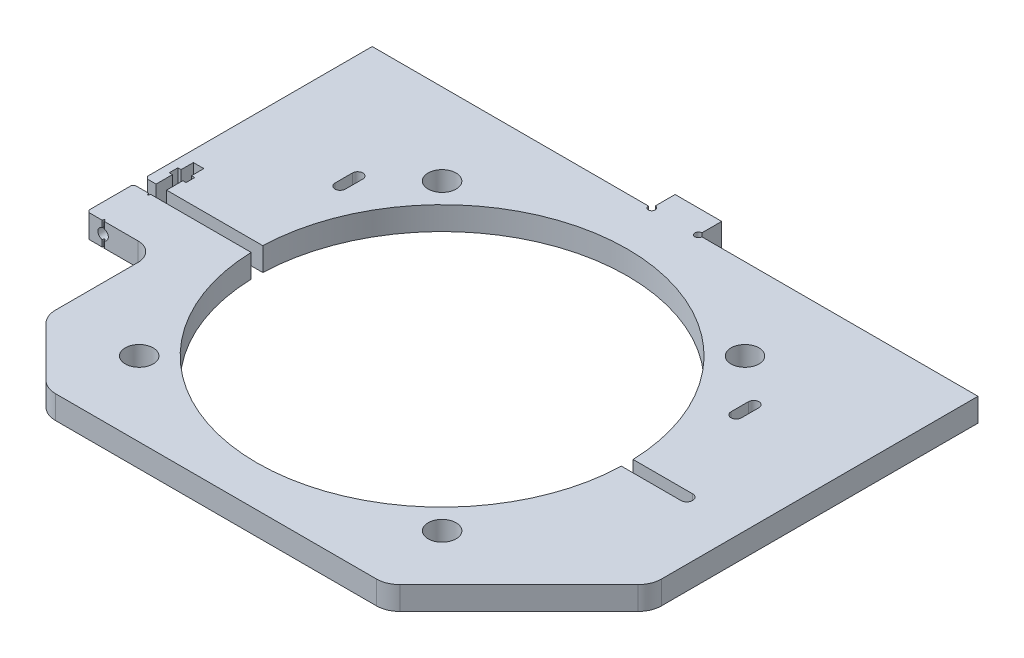
SolidWorks part; units mm, degrees
material "POLICARB. TRANSP."
ref_plane "Front Plane" through (0, 0, 0) normal (0, 0, 1) x (1, 0, 0)
ref_plane "Top Plane" through (0, 0, 0) normal (0, 1, 0) x (1, 0, 0)
ref_plane "Right Plane" through (0, 0, 0) normal (1, 0, 0) x (0, 0, -1)
sketch "Sketch1" plane through (0, 0, 0) normal (0, 1, 0) x (1, 0, 0)
  line L1 (130, 100) -> (-130, 100)
  line L2 (130, 100) -> (130, -100)
  line L3 (130, -100) -> (-130, -100)
  line L4 (-130, 100) -> (-130, -100)
  line L5 (0, -100) -> (0, 100) construction
  line L6 (130, 0) -> (-130, 0) construction
  point P0 (0, 0)
  dimension "D1" = 200
  dimension "D2" = 260
extrude "Extrude1" add sketch "Sketch1" along normal blind 10
sketch "Sketch2" plane through (0, 10, 0) normal (0, 1, 0) x (1, 0, 0)
  circle A0 centre (0, 0) radius 79.5
  dimension "D1" = 159
extrude "Extrude2" cut sketch "Sketch2" against normal blind 10
hole_wizard "M4 Clearance Hole2" positions "Sketch3" profile "Sketch4" size "M4" standard "DIN" slot yes
sketch "Sketch3" plane through (-130, 0, 100) normal (0, -1, 0) x (-1, 0, 0)
  line L0 (-215, 139) -> (-215, 151) construction
  line L1 (-260, 0) -> (-260, 200) construction
  line L2 (-260, 200) -> (0, 200) construction
  line L3 (0, 200) -> (0, 0) construction
  point P0 (-215, 145)
  point P5 (-45, 145)
  dimension "D1" = 12
  dimension "D2" = 45
  dimension "D3" = 55
  dimension "D4" = 45
sketch "Sketch4" plane through (85, 0, -45) normal (1, 0, 0) x (0, 0, -1)
  line L0 (0, 0) -> (0, 11.3519)
  line L1 (0, 11.3519) -> (2.25, 10)
  line L2 (2.25, 10) -> (2.25, 0)
  line L3 (2.25, 0) -> (0, 0)
  line L4 (0, 11.3519) -> (-2.25, 10) construction
  line L5 (0, -6.35) -> (0, 107.95) construction
  dimension "Hole Dia." = 4.5
  dimension "Hole Depth" = 10
  dimension "Drill Angle" = 118
sketch "Sketch5" plane through (0, 0, 0) normal (0, -1, 0) x (1, 0, 0)
  line L0 (-130, -100) -> (-130, 100) construction
  line L1 (-130, 2.5) -> (105, 2.5)
  line L2 (-130, 2.5) -> (-130, -2.5)
  line L3 (-130, -2.5) -> (105, -2.5)
  line L5 (0, 0) -> (130, 0) construction
  line L6 (130, 100) -> (130, -100) construction
  arc A0 (105, -2.5) -> (105, 2.5) centre (105, 0) ccw
  dimension "D1" = 5
  dimension "D2" = 235
extrude "Extrude3" cut sketch "Sketch5" against normal blind 10
sketch "Sketch6" plane through (0, 0, 0) normal (0, -1, 0) x (1, 0, 0)
  line L0 (-130, 2.5) -> (-130, 100) construction
  line L1 (-130, 100) -> (-100, 100)
  line L2 (-130, 100) -> (-130, 22.5)
  line L3 (-130, 22.5) -> (-100, 22.5)
  line L4 (-100, 100) -> (-100, 22.5)
  line L11 (-130, -2.5) -> (-79.4607, -2.5) construction
  line L12 (-130, 100) -> (130, 100) construction
  dimension "D1" = 25
  dimension "D2" = 30
extrude "Extrude4" cut sketch "Sketch6" against normal blind 10
fillet "Fillet1" radius 8 1 edges at (-100, 5, 22.5)
hole_wizard "M4 Clearance Hole3" positions "Sketch9" profile "Sketch10" hole size "M4" standard "DIN" end condition up to next
sketch "Sketch9" plane through (0, 0, 22.5) normal (0, 0, 1) x (1, 0, 0)
  line L0 (-115.8051, 10) -> (-115.8051, 0) construction
  line L1 (-130, 10) -> (-108, 10) construction
  line L2 (-130, 0) -> (-108, 0) construction
  line L4 (-115.8051, 5) -> (-130, 5) construction
  line L5 (-130, 10) -> (-130, 0) construction
  point P0 (-123, 5)
  dimension "D1" = 7
sketch "Sketch10" plane through (-123, 5, 22.5) normal (1, 0, 0) x (0, -1, 0)
  line L0 (0, 0) -> (0, 20)
  line L1 (0, 20) -> (2.25, 20)
  line L2 (2.25, 20) -> (2.25, 0)
  line L5 (2.25, 0) -> (0, 0)
  line L11 (0, -6.35) -> (0, 107.95) construction
  dimension "Thru Hole Dia." = 4.5
  dimension "Thru Hole Depth" = 20
sketch "Sketch11" plane through (0, 0, 0) normal (0, -1, 0) x (1, 0, 0)
  line L0 (-125.25, -2.5) -> (-125.25, -9.5)
  line L1 (-130, -2.5) -> (-79.4607, -2.5) construction
  line L2 (-125.25, -9.5) -> (-126.625, -9.5)
  line L3 (-126.625, -9.5) -> (-126.625, -13.2)
  line L4 (-126.625, -13.2) -> (-125.25, -13.2)
  line L5 (-125.25, -13.2) -> (-125.25, -18.5)
  line L6 (-125.25, -18.5) -> (-120.75, -18.5)
  line L7 (-120.75, -18.5) -> (-120.75, -13.2)
  line L8 (-120.75, -13.2) -> (-119.375, -13.2)
  line L9 (-119.375, -13.2) -> (-119.375, -9.5)
  line L10 (-119.375, -9.5) -> (-120.75, -9.5)
  line L11 (-120.75, -9.5) -> (-120.75, -2.5)
  line L12 (-120.75, -2.5) -> (-125.25, -2.5)
  line L13 (-123, -2.5) -> (-123, -18.5) construction
  line L14 (-130, -100) -> (-130, -2.5) construction
  dimension "D1" = 16
  dimension "D2" = 4.5
  dimension "D3" = 7.25
  dimension "D4" = 3.7
  dimension "D5" = 7
  dimension "D6" = 7
extrude "Extrude5" cut sketch "Sketch11" against normal blind 10
hole_wizard "Ø12.0 (12) Diameter Hole1" positions "Sketch12" profile "Sketch13" hole size "Ø12.0" standard "DIN" end condition through all
sketch "Sketch12" plane through (-130, 20, 100) normal (0, 1, 0) x (1, 0, 0)
  line L0 (130, -0.5617) -> (130, 200) construction
  line L3 (130, 200) -> (260, 100) construction
  line L5 (260, 100) -> (0, 100) construction
  line L6 (260, 200) -> (0, 200) construction
  line L7 (260, 0) -> (260, 200) construction
  point P0 (65, 165)
  point P2 (195, 165)
  point P4 (195, 35)
  point P6 (65, 35)
  dimension "D1" = 130
  dimension "D2" = 130
sketch "Sketch13" plane through (-65, 20, -65) normal (1, 0, 0) x (0, 0, 1)
  line L0 (0, 0) -> (0, 20)
  line L1 (0, 20) -> (6, 20)
  line L2 (6, 20) -> (6, 0)
  line L3 (6, 0) -> (0, 0)
  line L4 (0, -6.35) -> (0, 107.95) construction
  dimension "Thru Hole Dia." = 12
  dimension "Thru Hole Depth" = 20
chamfer "Chamfer1" distance 30 angle 45 1 edges at (-100, 5, 100)
fillet "Fillet3" [suppressed] radius 10
chamfer "Chamfer2" distance 1 angle 45 3 edges at (-130, 5, 22.5) (-130, 5, -2.5) (-130, 5, 2.5)
chamfer "Chamfer3" distance 60 angle 45 1 edges at (130, 5, 100)
sketch "Sketch16" plane through (0, 10, 0) normal (0, 1, 0) x (1, 0, 0)
  line L0 (-70, -100) -> (70, -100) construction
  line L1 (-73, -97) -> (73, -97)
  line L2 (-73, -97) -> (-73, -100)
  line L3 (-73, -100) -> (73, -100)
  line L4 (73, -97) -> (73, -100)
  line L5 (70, -100) -> (130, -40) construction
  line L6 (-100, -70) -> (-70, -100) construction
  dimension "D1" = 3
extrude "Extrude6" cut sketch "Sketch16" against normal blind 10
fillet "Fillet4" radius 10 4 edges at (73, 5, 97) (130, 5, 40) (-73, 5, 97) (-100, 5, 70)
sketch "Sketch17" plane through (0, 10, 0) normal (0, 1, 0) x (1, 0, 0)
  line L0 (-123.5, -2.5) -> (-123.5, -3.5) construction
  line L1 (-79.4607, -2.5) -> (-129, -2.5) construction
  line L2 (-123.5, -3.5) -> (-122.5, -3.5) construction
  line L3 (-122.5, -3.5) -> (-122.5, -2.5) construction
  line L4 (-122.5, -2.5) -> (-123.5, -2.5)
  line L5 (-123, 18.5) -> (-123, -22.5) construction
  line L6 (-125.25, 18.5) -> (-120.75, 18.5) construction
  line L7 (-129, -22.5) -> (-108, -22.5) construction
  line L8 (-123.5, -2.5) -> (-123, -3.5)
  line L9 (-123, -3.5) -> (-122.5, -2.5)
  dimension "D1" = 1
  dimension "D2" = 1
extrude "Extrude7" cut sketch "Sketch17" against normal blind 10
ref_plane "Plane1" through (0, 0, 12.5) normal (0, 0, -1) x (-1, 0, 0)
mirror "Mirror1" about plane through (0, 0, 12.5) normal (0, 0, -1) of "Extrude7"
sketch "Sketch18" plane through (0, 10, 0) normal (0, 1, 0) x (1, 0, 0)
  line L0 (130, 100) -> (-130, 100) construction
  line L1 (-10, 110) -> (10, 110)
  line L2 (-10, 110) -> (-10, 100)
  line L3 (-10, 100) -> (10, 100)
  line L4 (10, 110) -> (10, 100)
  line L5 (0, 0) -> (0, 79.5) construction
  arc A0 (79.4607, 2.5) -> (-79.4607, 2.5) centre (0, 0) ccw construction
  dimension "D1" = 20
  dimension "D2" = 10
extrude "Extrude8" add sketch "Sketch18" against normal blind 10
sketch "Sketch19" plane through (0, 10, 0) normal (0, 1, 0) x (1, 0, 0)
  line L0 (-11.5, 100) -> (-10, 100)
  line L1 (-10, 100) -> (-10, 101.5)
  line L2 (130, 100) -> (10, 100) construction
  line L3 (10, 101.5) -> (10, 100)
  line L4 (10, 100) -> (11.5, 100)
  arc A0 (-11.5, 100) -> (-10, 101.5) centre (-10, 100) ccw
  arc A1 (10, 101.5) -> (11.5, 100) centre (10, 100) ccw
  dimension "D1" = 3
extrude "Extrude9" cut sketch "Sketch19" against normal blind 10
